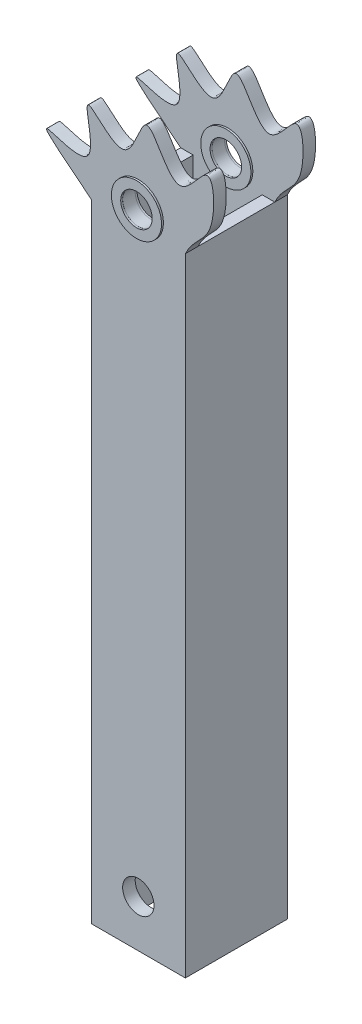
SolidWorks part; units mm, degrees
ref_plane "Front Plane" through (0, 0, 0) normal (0, 0, 1) x (1, 0, 0)
ref_plane "Top Plane" through (0, 0, 0) normal (0, 1, 0) x (1, 0, 0)
ref_plane "Right Plane" through (0, 0, 0) normal (1, 0, 0) x (0, 0, -1)
sketch "Sketch1" plane through (0, 0, 0) normal (0, 0, 1) x (1, 0, 0)
  line L1 (-19.05, -127) -> (19.05, -127)
  line L2 (-19.05, -127) -> (-19.05, 127)
  line L3 (-19.05, 127) -> (19.05, 127)
  line L4 (19.05, -127) -> (19.05, 127)
  line L5 (-19.05, -127) -> (19.05, 127) construction
  line L6 (-19.05, 127) -> (19.05, -127) construction
  point P0 (0, 0)
  dimension "D1" = 38.1
  dimension "D2" = 254
extrude "Boss-Extrude1" add sketch "Sketch1" against normal blind 20.6375
sketch "Sketch2" plane through (0, 127, 0) normal (0, 1, 0) x (1, 0, 0)
  line L0 (-13.97, 5.08) -> (-13.97, 20.6375)
  line L1 (-13.97, 20.6375) -> (13.97, 20.6375)
  line L2 (13.97, 20.6375) -> (13.97, 5.08)
  line L3 (13.97, 5.08) -> (-13.97, 5.08)
  line L4 (-19.05, 20.6375) -> (-19.05, 0) construction
  line L5 (19.05, 20.6375) -> (-19.05, 20.6375) construction
  line L6 (19.05, 20.6375) -> (19.05, 0) construction
  line L7 (19.05, 0) -> (-19.05, 0) construction
  dimension "D1" = 5.08
  dimension "D2" = 0
  dimension "D3" = 5.08
  dimension "D4" = 5.08
extrude "Cut-Extrude1" cut sketch "Sketch2" against normal through all
sketch "Sketch3" plane through (0, 0, 0) normal (0, 0, 1) x (1, 0, 0)
  line L4 (19.05, -127) -> (19.05, 127)
  line L5 (19.05, 127) -> (-19.05, 127)
  line L6 (-19.05, 127) -> (-19.05, -127)
  line L7 (-19.05, -127) -> (19.05, -127)
  line L8 (19.05, -127) -> (19.05, 127)
  line L10 (-19.05, 127) -> (-19.05, -127)
  line L11 (-19.05, -127) -> (19.05, -127)
  spline S0 degree 3 poles (-19.05, 127) (-56.0753, 156.2499) (-8.7651, 122.4559) (-26.7121, 171.1101) (-3.3846, 140.1027) (2.7759, 177.7478) (14.8126, 138.4291) (30.467, 168.5172) (31.839, 136.048) (22.2647, 133.9082) (19.05, 127) knots 0 0 0 0 0.207464 0.325923 0.435665 0.542831 0.674869 0.767185 0.882236 1 1 1 1
  dimension "D1" = 0
extrude "Boss-Extrude2" add sketch "Sketch3" against normal blind 5.08
sketch "Sketch4" plane through (0, 0, 0) normal (0, 0, 1) x (1, 0, 0)
  line L0 (19.05, -127) -> (19.05, 127) construction
  line L1 (-19.05, -127) -> (19.05, -127) construction
  circle A0 centre (0, 133.35) radius 6.35
  circle A1 centre (0, -107.95) radius 6.35
  point P6 (0, -127)
  dimension "D1" = 241.3
  dimension "D4" = 12.7
  dimension "D2" = 19.05
  dimension "D3" = 19.05
  dimension "D5" = 19.05
extrude "Cut-Extrude2" cut sketch "Sketch4" against normal through all
sketch "Sketch7" plane through (0, 0, -5.08) normal (0, 0, -1) x (-1, 0, 0)
  line L0 (-7.62, 133.35) -> (7.62, 133.35) construction
  circle A0 centre (0, 133.35) radius 10.16
  circle A1 centre (0, 133.35) radius 6.3754
  dimension "D1" = 0
ref_plane "Plane1" through (0, 0, -20.6375) normal (0, 0, 1) x (1, 0, 0)
mirror "Mirror1" about plane through (0, 0, -20.6375) normal (0, 0, 1) of "Cut-Extrude1", "Boss-Extrude1", "Cut-Extrude2", "Boss-Extrude2"
sketch "Sketch5" plane through (0, 0, 0) normal (0, 0, 1) x (1, 0, 0)
  line L0 (-7.62, 133.35) -> (7.62, 133.35) construction
  circle A0 centre (0, 133.35) radius 10.16
  circle A1 centre (0, 133.35) radius 6.3754
sketch "Sketch6" plane through (0, 0, -41.275) normal (0, 0, -1) x (-1, 0, 0)
  line L0 (-7.62, 133.35) -> (7.62, 133.35) construction
  circle A0 centre (0, 133.35) radius 10.16
  circle A1 centre (0, 133.35) radius 6.3754
sketch "Sketch8" plane through (0, 0, -36.195) normal (0, 0, 1) x (1, 0, 0)
  line L0 (-7.62, 133.35) -> (7.62, 133.35) construction
  circle A0 centre (0, 133.35) radius 10.16
  circle A3 centre (0, 133.35) radius 6.3754
extrude "Boss-Extrude7" add sketch "Sketch7" along normal blind 0.762
extrude "Boss-Extrude8" add sketch "Sketch5" along normal blind 0.762
extrude "Boss-Extrude9" add sketch "Sketch8" along normal blind 0.762
extrude "Boss-Extrude10" add sketch "Sketch6" along normal blind 0.762
